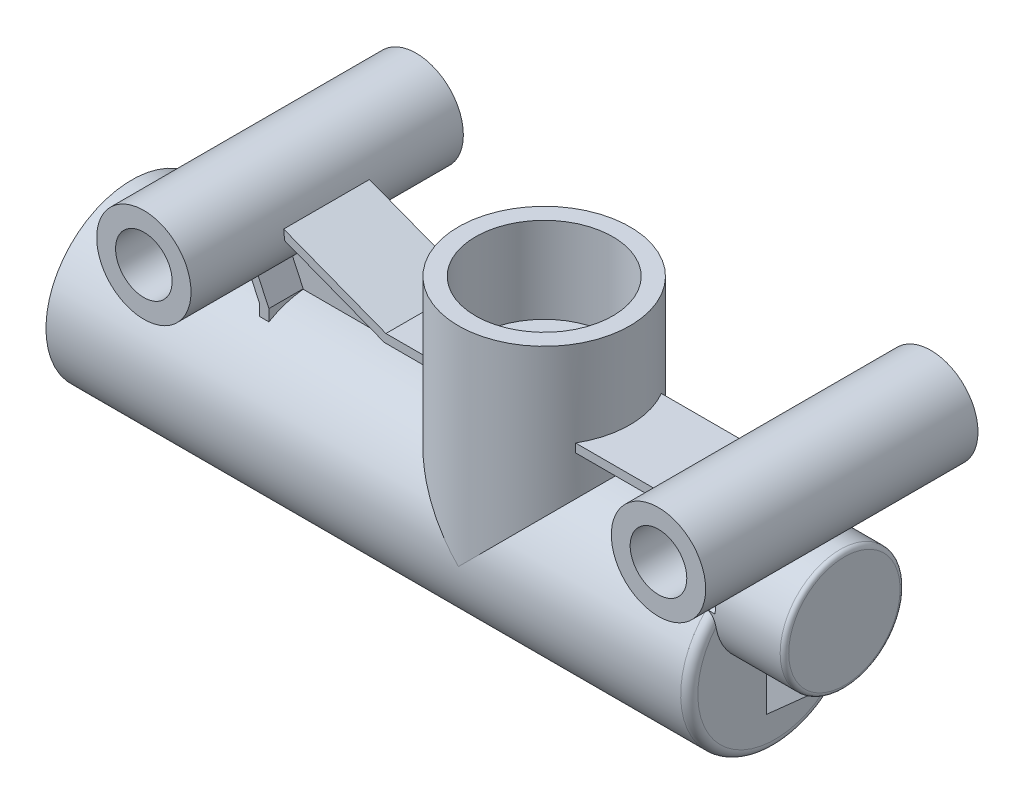
SolidWorks part; units mm, degrees
ref_plane "Front Plane" through (0, 0, 0) normal (0, 0, 1) x (1, 0, 0)
ref_plane "Top Plane" through (0, 0, 0) normal (0, 1, 0) x (1, 0, 0)
ref_plane "Right Plane" through (0, 0, 0) normal (1, 0, 0) x (0, 0, -1)
sketch "Sketch1" plane through (0, 0, 0) normal (0, 0, 1) x (1, 0, 0)
  line L0 (0, 12.7) -> (0, 10.16)
  line L1 (0, 12.7) -> (95.25, 12.7)
  line L2 (0, 0) -> (115.4663, 0) construction
  line L3 (95.25, 12.7) -> (95.25, 0)
  line L5 (105.522, 8.8791) -> (105.522, 17.7581)
  line L6 (105.522, 17.7581) -> (95.25, 17.7581)
  line L7 (95.25, 17.7581) -> (95.25, 12.7)
  line L8 (0, 10.16) -> (2.54, 10.16)
  line L9 (2.54, 10.16) -> (2.54, 0)
  line L10 (105.522, 8.8791) -> (95.25, 8.8791) construction
  line L11 (95.25, 8.8791) -> (105.522, 8.8791)
  line L12 (2.54, 0) -> (95.25, 0)
  line L13 (95.25, 17.7581) -> (95.25, 12.7)
  line L14 (95.25, 0) -> (95.25, -7.5808)
  line L15 (95.25, -7.5808) -> (103.7607, 0)
  line L17 (103.7607, 0) -> (103.7607, 1.6748)
  line L18 (103.7607, 1.6748) -> (95.25, 1.6748)
  line L19 (95.25, 1.6748) -> (95.25, 0)
  point P4 (0, 0)
  dimension "D1" = 12.7
  dimension "D2" = 2.54
  dimension "D3" = 2.54
  dimension "D4" = 95.25
revolve "Revolve1" add sketch "Sketch1" angle 360 about L12 region at (48.6355, 6.3777, 0)
revolve "Revolve2" add sketch "Sketch1<3>" angle 360 about L11 region at (100.386, 13.3186, 0)
sketch "Sketch1<3>" plane through (0, 0, 0) normal (0, 0, 1) x (1, 0, 0) same geometry as "Sketch1"
fillet "Fillet1" radius 1.27 1 edges at (95.25, -12.7, 0)
fillet "Fillet2" radius 0.635 1 edges at (105.522, 8.8791, 8.8791)
extrude "Boss-Extrude3" add sketch "Sketch1<5>" along normal mid plane 2.54 contours L17 L18 L3 L14 L15 region at (98.5216, -1.496, 0)
sketch "Sketch1<5>" plane through (0, 0, 0) normal (0, 0, 1) x (1, 0, 0) same geometry as "Sketch1"
sketch "Sketch2" plane through (0, 0, 0) normal (0, 0, 1) x (1, 0, 0)
  line L0 (21.956, 22.86) -> (98.156, 22.86) construction
  line L1 (0, 0) -> (129.264, 0) construction
  line L2 (105.522, 0.635) -> (105.522, 17.1231) construction
  line L3 (105.522, 0.635) -> (105.522, 17.1231) construction
  line L4 (28.848, 23.9962) -> (43.9879, 18.1706)
  line L5 (43.9879, 18.1706) -> (89.4132, 18.1706)
  line L6 (89.4132, 18.1706) -> (91.4007, 21.0834)
  line L7 (28.9362, 22.6015) -> (43.752, 16.9006)
  line L8 (43.752, 16.9006) -> (90.0842, 16.9006)
  line L9 (90.0842, 16.9006) -> (91.9557, 19.6435)
  line L11 (28.3919, 22.8109) -> (43.752, 16.9006) construction
  line L12 (90.0842, 16.9006) -> (92.4498, 20.3676) construction
  line L13 (95.25, 17.7581) -> (95.25, 9.0826) construction
  line L15 (95.25, 16.5082) -> (95.25, 12.7)
  line L16 (26.6568, 12.7) -> (24.889, 16.5206)
  line L17 (25.2574, 12.7) -> (23.6875, 16.093)
  line L18 (25.5041, 12.1667) -> (23.7364, 15.9874) construction
  line L19 (23.6875, 16.093) -> (23.4912, 16.5206)
  line L20 (23.4912, 16.5206) -> (24.7143, 16.9006)
  line L21 (24.7143, 16.9006) -> (24.889, 16.5206)
  line L22 (28.848, 23.9962) -> (28.0852, 23.9962)
  line L23 (28.0852, 23.9962) -> (28.4666, 22.6015)
  line L24 (28.4666, 22.6015) -> (28.848, 22.6015)
  line L25 (91.4007, 21.0834) -> (92.6519, 21.4295)
  line L26 (92.6519, 21.4295) -> (92.6519, 19.8652)
  line L27 (92.6519, 19.8652) -> (91.9557, 19.6435)
  line L28 (25.2574, 12.7) -> (25.2574, 10.9851)
  line L29 (25.2574, 10.9851) -> (26.6568, 10.9851)
  line L30 (26.6568, 10.9851) -> (26.6568, 12.7)
  line L31 (26.6568, 10.9851) -> (95.25, 10.9851)
  line L32 (95.25, 10.9851) -> (95.25, 12.7)
  circle A0 centre (98.156, 22.86) radius 4.191
  circle A1 centre (21.956, 22.86) radius 4.191
  circle A2 centre (98.156, 22.86) radius 6.985
  circle A3 centre (21.956, 22.86) radius 6.985
  dimension "D1" = 8.382
  dimension "D3" = 76.2
  dimension "D5" = 13.97
  dimension "D2" = 22.86
  dimension "D4" = 7.366
  dimension "D6" = 1.27
  dimension "D7" = 1.27
extrude "Boss-Extrude4" add sketch "Sketch2" along normal mid plane 40.3225 contours A3 A1 | A2 A0 | L25 A2 L27 L26 | L19 A3 L21 L20 region at (28.7208, 23.4139, 0) region at (24.1882, 16.496, 0) region at (97.2856, 29.5914, 0) region at (92.1365, 20.5693, 0)
extrude "Boss-Extrude7" add sketch "Sketch2<4>" along normal mid plane 12.7 contours A3 L7 L8 L9 A2 L6 L5 L4 region at (36.1899, 20.4907, 0)
sketch "Sketch2<4>" plane through (0, 0, 0) normal (0, 0, 1) x (1, 0, 0) same geometry as "Sketch2"
extrude "Boss-Extrude9" add sketch "Sketch2<6>" along normal mid plane 12.7 contours L16 L21 L20 L19 L17 L28 L29 L30
sketch "Sketch2<6>" plane through (0, 0, 0) normal (0, 0, 1) x (1, 0, 0) same geometry as "Sketch2"
extrude "Boss-Extrude10" add sketch "Sketch2<8>" along normal mid plane 2.54 contours A3 L16 L30 L31 L32 L15 A2 L9 L8 L7 region at (58.1291, 14.4973, 0)
sketch "Sketch2<8>" plane through (0, 0, 0) normal (0, 0, 1) x (1, 0, 0) same geometry as "Sketch2"
sketch "Sketch3" plane through (2.54, 0, 0) normal (-1, 0, 0) x (0, 0, 1)
  circle A0 centre (0, 0) radius 3.9688
  dimension "D1" = 7.9375
extrude "Cut-Extrude1" cut sketch "Sketch3" against normal blind 64.77
sketch "Sketch4" plane through (0, 0, 0) normal (0, 0, 1) x (1, 0, 0)
  line L0 (2.54, 0) -> (9.8239, 0) construction
  line L1 (2.54, 10.16) -> (2.54, -10.16) construction
  circle A0 centre (6.1819, 0) radius 3.175
revolve "Revolve4" [suppressed] add sketch "Sketch4" angle 360 about L0
sketch "Sketch5" [suppressed] plane through (0, 0, 0) normal (0, 0, 1) x (1, 0, 0)
  line L0 (6.1819, 3.175) -> (6.1819, 3.683)
  line L1 (6.1819, 3.683) -> (0, 3.683)
  line L2 (0, 12.7) -> (0, -12.7) construction
  line L3 (0, 3.683) -> (0, -3.683)
  line L4 (0, -3.683) -> (6.1819, -3.683)
  line L6 (6.1819, -3.683) -> (6.1819, -3.175)
  line L7 (0, 0) -> (3.0069, 0) construction
  line L8 (0, 0) -> (3.0069, 0)
  line L9 (0, 0) -> (-119.014, 0)
  line L10 (105.522, 0.635) -> (105.522, 17.1231) construction
  line L11 (-119.014, 0) -> (-119.014, 3.9687)
  line L12 (-119.014, 3.9687) -> (0, 3.9687)
  line L13 (0, 3.683) -> (0, 3.9687)
  line L14 (0, 3.9687) -> (0, 3.683)
  circle A0 centre (6.1819, 0) radius 3.175 construction
  arc A1 (6.1819, 3.175) -> (6.1819, -3.175) centre (6.1819, 0) ccw
  dimension "D1" = 0.508
  dimension "D2" = 0.508
  dimension "D3" = 224.536
  dimension "D4" = 3.9688
revolve "Revolve6" [suppressed] add sketch "Sketch5" angle 360 about L7
sketch "Sketch6" plane through (0, 18.1706, 0) normal (0, 1, 0) x (1, 0, 0)
  line L0 (105.522, -8.2441) -> (105.522, 8.2441) construction
  circle A0 centre (61.072, 0) radius 12.7
  dimension "D1" = 44.45
extrude "Boss-Extrude11" add sketch "Sketch6" along normal blind 12.7 and the other way up to surface other way up to face at (57.7969, 9.5736, 0)
sketch "Sketch7" plane through (0, 30.8706, 0) normal (0, 1, 0) x (1, 0, 0)
  circle A0 centre (61.072, 0) radius 10.16
extrude "Cut-Extrude2" cut sketch "Sketch7" against normal up to surface (12.7 mm away) up to face at (46.6053, 18.1706, 0)
sketch3d "3DSketch1"
  line L0 (0, 0, 0) -> (6.35, 0, 0) construction
  line L1 (6.35, 0, 0) -> (34.925, 0, 0)
  dimension "D1" = 6.35
  dimension "D2" = 28.575
sketch3d "3DSketch2"
  line L0 (21.956, 22.86, 20.1612) -> (21.956, 22.86, -20.1612) construction
  line L1 (21.956, 22.86, 20.1612) -> (21.956, 22.86, -20.1612) construction
sketch3d "3DSketch3"
  line L0 (98.156, 22.86, 20.1612) -> (98.156, 22.86, -20.1612) construction
  line L1 (98.156, 22.86, 20.1612) -> (98.156, 22.86, -20.1612) construction
